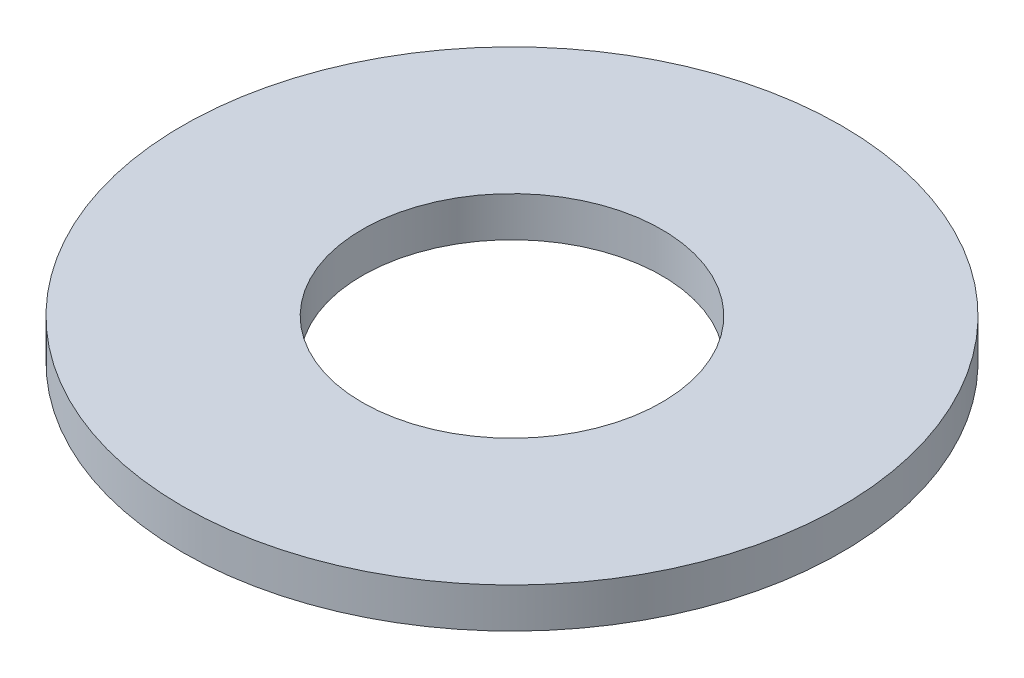
SolidWorks part; units mm, degrees
ref_plane "Front Plane" through (0, 0, 0) normal (0, 0, 1) x (1, 0, 0)
ref_plane "Top Plane" through (0, 0, 0) normal (0, 1, 0) x (1, 0, 0)
ref_plane "Right Plane" through (0, 0, 0) normal (1, 0, 0) x (0, 0, -1)
sketch "Sketch1" plane through (0, 0, 0) normal (0, 1, 0) x (1, 0, 0)
  circle A0 centre (0, 0) radius 82.5
  dimension "FLANGE_OD" = 165
extrude "Boss-Extrude1" add sketch "Sketch1" along normal blind 10
sketch "Sketch2" plane through (0, 0, 0) normal (0, 1, 0) x (1, 0, 0)
  circle A0 centre (0, 0) radius 37.5
  dimension "BORE_D" = 75
extrude "Cut-Extrude1" cut sketch "Sketch2" along normal through all
sketch "Sketch3" plane through (0, 10, 0) normal (0, 1, 0) x (1, 0, 0)
  circle A0 centre (0, 0) radius 27.4574 construction
  circle A1 centre (-27.4574, 0) radius 6.9125
  dimension "BOLT_D" = 13.825
  dimension "BOLT_PCD" = 54.9148
extrude "Cut-Extrude2" cut sketch "Sketch3" against normal blind 6.8843 rebuild error yes
pattern_circular "CirPattern1" count 3 over 360 rebuild error yes
